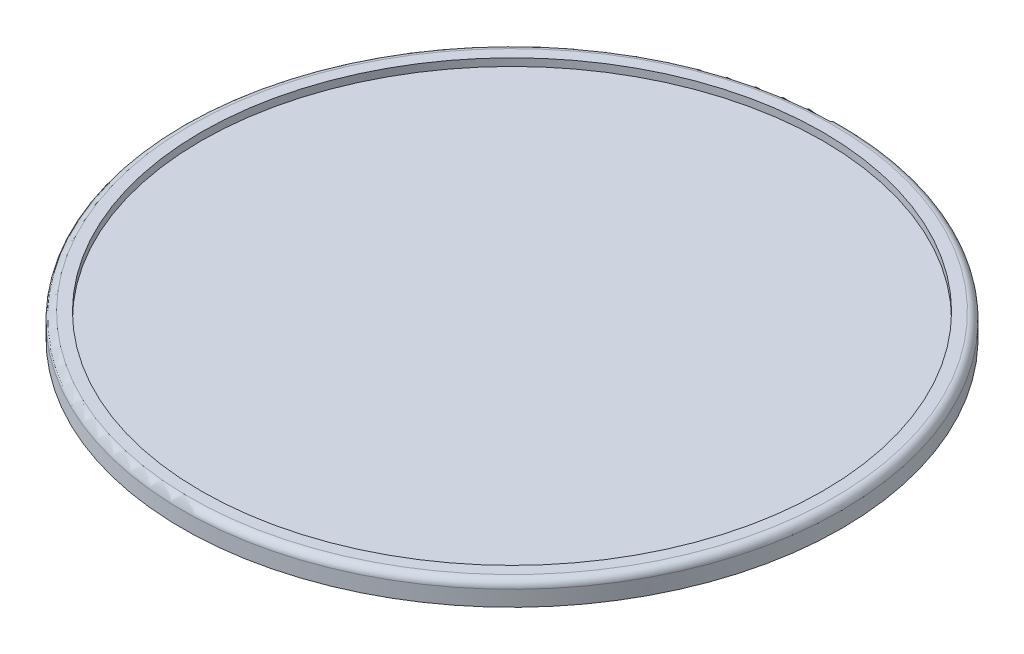
SolidWorks part; units mm, degrees
ref_plane "Front Plane" through (0, 0, 0) normal (0, 0, 1) x (1, 0, 0)
ref_plane "Top Plane" through (0, 0, 0) normal (0, 1, 0) x (1, 0, 0)
ref_plane "Right Plane" through (0, 0, 0) normal (1, 0, 0) x (0, 0, -1)
sketch "Sketch1" plane through (0, 0, 0) normal (0, 0, 1) x (1, 0, 0)
  line L0 (0, 0) -> (33.528, 0)
  line L1 (33.528, 0) -> (33.528, -2.3495)
  line L2 (33.528, -2.3495) -> (20.5232, -2.3495)
  line L3 (20.5232, -2.3495) -> (20.5232, -9.017)
  line L4 (20.5232, -9.017) -> (14.0462, -9.017)
  line L5 (14.0462, -9.017) -> (14.0462, -2.3495)
  line L6 (14.0462, -2.3495) -> (0, -2.3495)
  line L7 (0, -2.3495) -> (0, 0)
  line L8 (0, 0) -> (0, 41.1062) construction
  dimension "D1" = 67.056
  dimension "D2" = 2.3495
  dimension "D3" = 6.477
  dimension "D4" = 9.017
  dimension "D5" = 41.0464
revolve "Revolve1" add sketch "Sketch1" angle 360 about L8
fillet "Fillet1" radius 0.762 1 edges at (33.528, 0, 0)
sketch "Sketch2" plane through (0, 0, 0) normal (0, 1, 0) x (1, 0, 0)
  circle A0 centre (0, 0) radius 31.623
  circle A5 centre (0, 0) radius 33.528 construction
  dimension "D1" = 1.905
extrude "Cut-Extrude1" cut sketch "Sketch2" against normal blind 0.762
sketch "Sketch3" plane through (0, -9.017, 0) normal (0, -1, 0) x (1, 0, 0)
  line L0 (0, 0) -> (0, 35.4425) construction
  line L1 (0, 0) -> (-18.4981, 32.0397) construction
  line L2 (-8.8468, 16.2376) -> (-7.1317, 13.2668)
  line L3 (-0.4572, 18.4855) -> (-0.4572, 15.0553)
  circle A2 centre (0, 0) radius 18.4912
  arc A3 (-0.4572, 18.4855) -> (-8.8468, 16.2376) centre (0, 0) ccw
  circle A5 centre (0, 0) radius 15.0622
  arc A6 (-0.4572, 15.0553) -> (-7.1317, 13.2668) centre (0, 0) ccw
  dimension "D3" = 30
  dimension "D4" = 0.9144
  dimension "D5" = 0.9144
  dimension "D1" = 2.032
  dimension "D2" = 1.016
extrude "Cut-Extrude2" cut sketch "Sketch3" against normal blind 7.112
ref_axis "Axis1" through (0, -2.3495, 0) along (0, -1, 0)
pattern_circular "CirPattern1" count 12 over 360 about axis through (0, -2.3495, 0) along (0, -1, 0) of "Cut-Extrude2"
